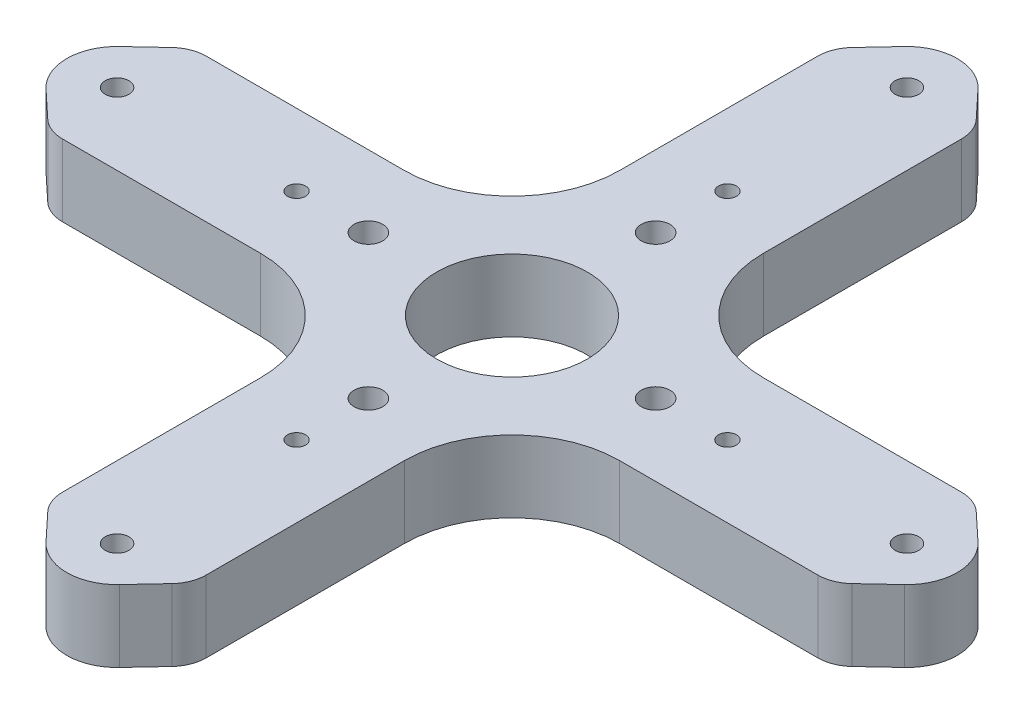
SolidWorks part; units mm, degrees
material "AISI 316 Stainless Steel Sheet (SS)"
ref_plane "Front Plane" through (0, 0, 0) normal (0, 0, 1) x (1, 0, 0)
ref_plane "Top Plane" through (0, 0, 0) normal (0, 1, 0) x (1, 0, 0)
ref_plane "Right Plane" through (0, 0, 0) normal (1, 0, 0) x (0, 0, -1)
sketch "Sketch1" plane through (0, 0, 0) normal (0, 1, 0) x (1, 0, 0)
  line L17 (10, 10) -> (54.5563, 10)
  line L18 (54.5563, 10) -> (59.7818, 5.1122)
  line L19 (10, -10) -> (54.5563, -10)
  line L20 (54.5563, -10) -> (59.7818, -5.1122)
  line L21 (55, 0) -> (0, 0) construction
  line L22 (54.5563, 10) -> (54.5563, -10) construction
  line L23 (10, -10) -> (10, -54.5563)
  line L24 (10, -54.5563) -> (5.1122, -59.7818)
  line L25 (-10, -54.5563) -> (-5.1122, -59.7818)
  line L26 (-10, -10) -> (-10, -54.5563)
  line L27 (-10, -10) -> (-54.5563, -10)
  line L28 (-54.5563, -10) -> (-59.7818, -5.1122)
  line L29 (-54.5563, 10) -> (-59.7818, 5.1122)
  line L30 (-10, 10) -> (-54.5563, 10)
  line L31 (-10, 10) -> (-10, 54.5563)
  line L32 (-10, 54.5563) -> (-5.1122, 59.7818)
  line L33 (10, 54.5563) -> (5.1122, 59.7818)
  line L34 (10, 10) -> (10, 54.5563)
  circle A0 centre (-20, 0) radius 2
  circle A1 centre (0, 20) radius 2
  circle A2 centre (20, 0) radius 2
  circle A3 centre (0, -20) radius 2
  circle A4 centre (0, 0) radius 10.5
  arc A5 (59.7818, 5.1122) -> (59.7818, -5.1122) centre (55, 0) cw
  circle A6 centre (0, 0) radius 60 construction
  arc A7 (5.1122, -59.7818) -> (-5.1122, -59.7818) centre (0, -55) cw
  arc A8 (-59.7818, -5.1122) -> (-59.7818, 5.1122) centre (-55, 0) cw
  arc A9 (-5.1122, 59.7818) -> (5.1122, 59.7818) centre (0, 55) cw
  point P30 (0, 0)
  point P49 (0, 0)
  dimension "D2" = 4
  dimension "D6" = 21
  dimension "D4" = 7
  dimension "D5" = 120
  dimension "D1" = 20
  dimension "D3" = 4
  dimension "D7" = 20
  dimension "D9" = 55
  dimension "D8" = 4
extrude "Boss-Extrude1" add sketch "Sketch1" along normal blind 10
fillet "Fillet1" radius 15 4 edges at (-10, 5, 10) (-10, 5, -10) (10, 5, -10) (10, 5, 10)
fillet "Fillet2" radius 5 8 edges at (-54.5563, 5, 10) (-54.5563, 5, -10) (-10, 5, -54.5563) (10, 5, -54.5563) (54.5563, 5, -10) (54.5563, 5, 10) (-10, 5, 54.5563) (10, 5, 54.5563)
hole_wizard "M4x0.7 Tapped Hole1" positions "Sketch2" profile "Sketch3" tap size "M4x0.7" standard "ANSI Metric" end condition through all
sketch "Sketch2" plane through (0, 0, 0) normal (0, -1, 0) x (-1, 0, 0)
  point P0 (0, -55)
  point P3 (-55, 0)
  point P6 (0, 55)
  point P9 (55, 0)
sketch "Sketch3" plane through (0, 0, 55) normal (1, 0, 0) x (0, 0, -1)
  line L0 (0, 0) -> (0, 10)
  line L1 (0, 10) -> (1.65, 10)
  line L2 (1.65, 10) -> (1.65, 0)
  line L5 (1.65, 0) -> (0, 0)
  line L11 (0, -6.35) -> (0, 107.95) construction
  dimension "Thru Tap Drill Dia." = 3.3
  dimension "Thru Tap Drill Depth" = 10
cosmetic thread "Hole Thread1" parameters "D2"=4
cosmetic thread "Hole Thread2" parameters "D2"=4
cosmetic thread "Hole Thread3" parameters "D2"=4
cosmetic thread "Hole Thread4" parameters "D2"=4
hole_wizard "M3x0.5 Tapped Hole1" positions "Sketch4" profile "Sketch5" tap size "M3x0.5" standard "ANSI Metric" end condition through all
sketch "Sketch4" plane through (0, 0, 0) normal (0, -1, 0) x (-1, 0, 0)
  line L0 (0, -55) -> (0, 0) construction
  point P0 (0, -30)
  point P15 (-30, 0)
  point P16 (0, 30)
  point P17 (30, 0)
  point P18 (0, 0)
  dimension "D1" = 30
  dimension "D2" = 4
sketch "Sketch5" plane through (0, 0, 30) normal (1, 0, 0) x (0, 0, -1)
  line L0 (0, 0) -> (0, 10)
  line L1 (0, 10) -> (1.25, 10)
  line L2 (1.25, 10) -> (1.25, 0)
  line L5 (1.25, 0) -> (0, 0)
  line L11 (0, -6.35) -> (0, 107.95) construction
  dimension "Thru Tap Drill Dia." = 2.5
  dimension "Thru Tap Drill Depth" = 10
cosmetic thread "Hole Thread5" parameters "D2"=3
cosmetic thread "Hole Thread6" parameters "D2"=3
cosmetic thread "Hole Thread7" parameters "D2"=3
cosmetic thread "Hole Thread8" parameters "D2"=3
